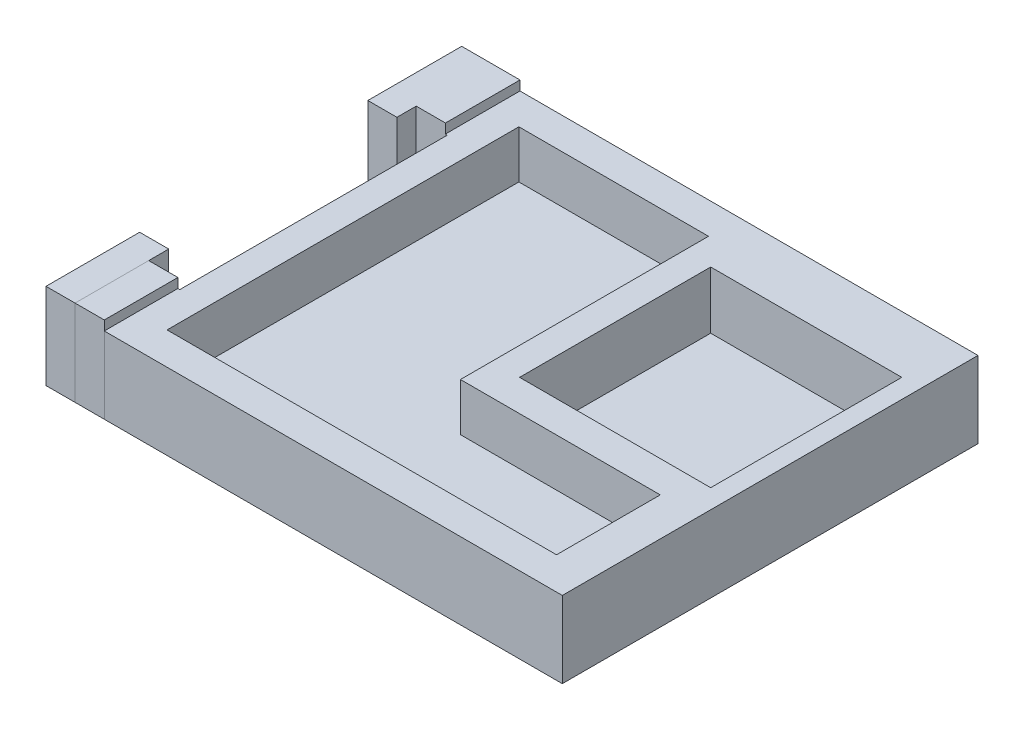
SolidWorks part; units mm, degrees
note: The reader was unsure of these and kept them because the rebuilt part matched: shared geometry of "Эскиз1<4>".
ref_plane "Спереди" through (0, 0, 0) normal (0, 0, 1) x (1, 0, 0)
ref_plane "Сверху" through (0, 0, 0) normal (0, 1, 0) x (1, 0, 0)
ref_plane "Справа" through (0, 0, 0) normal (1, 0, 0) x (0, 0, -1)
sketch "Эскиз1" plane through (0, 0, 0) normal (0, 1, 0) x (1, 0, 0)
  line L0 (-48.6142, 31.7159) -> (-48.6142, -11.7841)
  line L1 (-22.8851, 25.7432) -> (-2.8851, 25.7432)
  line L2 (-22.8851, 25.7432) -> (-22.8851, 5.7432)
  line L3 (-22.8851, 5.7432) -> (-2.8851, 5.7432)
  line L4 (-2.8851, 25.7432) -> (-2.8851, 5.7432)
  line L5 (-48.6142, -11.7841) -> (-0.8851, -11.7841)
  line L6 (-0.8851, 31.7159) -> (-0.8851, -11.7841)
  line L7 (-48.6142, 31.7159) -> (-0.8851, 31.7159)
  line L8 (-48.6142, -11.7841) -> (18.8858, -11.7841) construction
  line L9 (-48.6142, 31.7159) -> (-48.6142, -11.7841) construction
  line L10 (-48.6142, 31.7159) -> (18.8858, 31.7159) construction
extrude "Бобышка-Вытянуть1" add sketch "Эскиз1" against normal blind 2 contours L7 L6 L5 L0
extrude "Бобышка-Вытянуть2" add sketch "Эскиз1<4>" along normal blind 6
sketch "Эскиз1<4>" plane through (0, 0, 0) normal (0, 1, 0) x (1, 0, 0) same geometry as "Эскиз1"
sketch "Эскиз6" plane through (0, 6, 0) normal (0, 1, 0) x (1, 0, 0)
  line L0 (-48.6142, -11.7841) -> (-0.8851, -11.7841) construction
  line L1 (-51.872, -4.0816) -> (-48.8142, -4.0816)
  line L2 (-51.872, -4.0816) -> (-51.872, -11.7841)
  line L3 (-51.872, -11.7841) -> (-48.8142, -11.7841)
  line L4 (-48.8142, -4.0816) -> (-48.8142, -11.7841)
extrude "Бобышка-Вытянуть5" add sketch "Эскиз6" along normal offset from surface 0.2 and the other way up to surface (8 mm away) contours L4 L3 L2 L1 other way up to face at (-24.7497, -2, -9.9659)
sketch "Эскиз5" plane through (0, 0, 11.7841) normal (0, 0, 1) x (1, 0, 0)
  line L0 (-51.872, 7) -> (-48.8142, 7) construction
  line L1 (-51.872, 7) -> (-54.9142, 7)
  line L2 (-51.872, 7) -> (-51.872, -2)
  line L3 (-51.872, -2) -> (-54.9142, -2)
  line L4 (-54.9142, 7) -> (-54.9142, -2)
  line L5 (-48.6142, -2) -> (-0.8851, -2) construction
extrude "Бобышка-Вытянуть6" add sketch "Эскиз5" against normal offset from surface (9.8 mm away) 0.2
sketch "Эскиз7" plane through (0, 6, 0) normal (0, 1, 0) x (1, 0, 0)
  line L0 (-48.8142, -4.0816) -> (-48.8142, -11.7841) construction
  line L1 (-54.9142, 31.7159) -> (-48.8142, 31.7159)
  line L2 (-54.9142, 31.7159) -> (-54.9142, 23.9159)
  line L3 (-51.872, 23.9159) -> (-48.8142, 23.9159)
  line L4 (-48.8142, 31.7159) -> (-48.8142, 23.9159)
  line L5 (-51.872, -1.9841) -> (-51.872, -11.7841) construction
  line L6 (-0.8851, 31.7159) -> (-48.6142, 31.7159) construction
  line L9 (-54.9142, 23.9159) -> (-54.9142, 21.8957)
  line L10 (-54.9142, 21.8957) -> (-51.872, 21.8957)
  line L11 (-51.872, 23.9159) -> (-51.872, 21.8957)
  line L12 (-54.9142, -1.9841) -> (-54.9142, -11.7841) construction
extrude "Бобышка-Вытянуть7" add sketch "Эскиз7" along normal up to surface and the other way up to surface contours L2 L9 L10 L11 L3 L4 L1
sketch "Эскиз3" plane through (-48.6142, 0, 0) normal (-1, 0, 0) x (0, 0, 1)
  line L1 (-31.7159, -2) -> (11.7841, -2) construction
  line L2 (-31.7159, 6) -> (-23.9159, 6)
  line L3 (-31.7159, 6) -> (-31.7159, -2)
  line L4 (-31.7159, -2) -> (-23.9159, -2)
  line L5 (-23.9159, 6) -> (-23.9159, -2)
  line L7 (11.7841, 6) -> (4.0816, 6)
  line L8 (11.7841, 6) -> (11.7841, -2)
  line L9 (11.7841, -2) -> (4.0816, -2)
  line L10 (4.0816, 6) -> (4.0816, -2)
  line L11 (-31.7159, 6) -> (11.7841, 6) construction
  line L12 (-23.9159, 7) -> (-23.9159, -2) construction
extrude "Бобышка-Вытянуть3" add sketch "Эскиз3" along normal up to next (0.2 mm away)
sketch "Эскиз8" plane through (0, 6, 0) normal (0, 1, 0) x (1, 0, 0)
  line L1 (-45.6274, 28.4126) -> (-25.7828, 28.4126)
  line L2 (-45.6274, 28.4126) -> (-45.6274, -8.4033)
  line L3 (-45.6274, -8.4033) -> (-25.7828, -8.4033)
  line L4 (-25.7828, 28.4126) -> (-25.7828, 2.4533)
  line L5 (-25.7828, -8.4033) -> (-4.8721, -8.4033)
  line L7 (-25.7828, 2.4533) -> (-4.8721, 2.4533)
  line L8 (-4.8721, -8.4033) -> (-4.8721, 2.4533)
extrude "Вырез-Вытянуть1" cut sketch "Эскиз8" against normal offset from surface (5 mm away) 3 contours L2 L3 L5 L8 L7 L4 L1 up to face at (-36.7945, -2, -11.6913)
